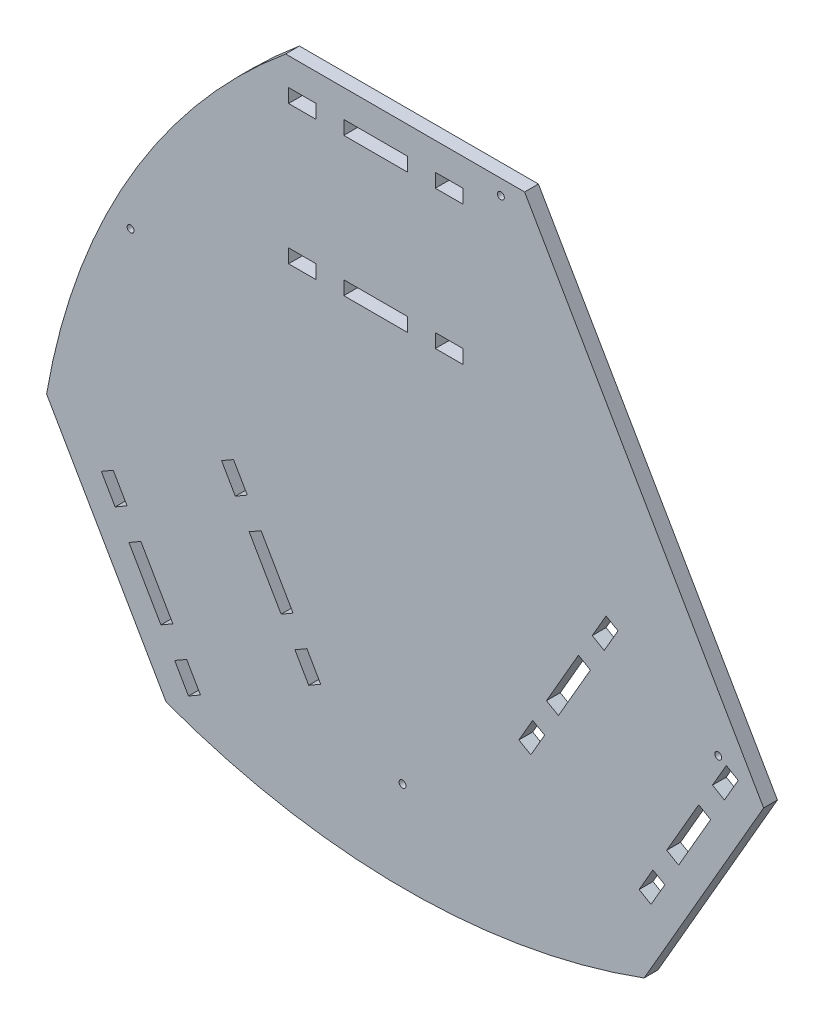
SolidWorks part; units mm, degrees
ref_plane "Front Plane" through (0, 0, 0) normal (0, 0, 1) x (1, 0, 0)
ref_plane "Top Plane" through (0, 0, 0) normal (0, 1, 0) x (1, 0, 0)
ref_plane "Right Plane" through (0, 0, 0) normal (1, 0, 0) x (0, 0, -1)
sketch "Sketch1" plane through (0, 0, 0) normal (0, 0, 1) x (0.866, -0.5, 0)
  line L0 (125, -43.3013) -> (125, 43.3013)
  line L1 (-100, 86.6025) -> (-100, -86.6025)
  line L2 (-25, -129.9038) -> (125, -43.3013)
  line L3 (125, 43.3013) -> (-25, 129.9038)
  line L4 (-25, 129.9038) -> (-100, 86.6025)
  line L5 (-100, -86.6025) -> (-25, -129.9038)
  circle A0 centre (0, 0) radius 100 construction
  dimension "D1" = 200
  dimension "D2" = 225
  dimension "D3" = 3
extrude "Boss-Extrude1" add sketch "Sketch1" along normal blind 5
sketch "Sketch2" plane through (0, 0, 5) normal (0, 0, 1) x (1, 0, 0)
  line L0 (7.45, 112.5) -> (13.95, 112.5) construction
  line L1 (-25, 107.5) -> (25, 107.5)
  line L2 (-25, 107.5) -> (-25, 67.5)
  line L3 (-25, 67.5) -> (25, 67.5)
  line L4 (25, 107.5) -> (25, 67.5)
  line L5 (-42.2219, 115) -> (-37.2219, 115)
  line L6 (-42.2219, 115) -> (-42.2219, 110)
  line L7 (-42.2219, 110) -> (-37.2219, 110)
  line L8 (-37.2219, 115) -> (-37.2219, 110)
  line L9 (-24.55, 115) -> (-14.55, 115)
  line L10 (-105.5977, -32.0994) -> (-45.9567, -55.4006) construction
  line L11 (105.5977, -32.0994) -> (80.5977, -75.4006)
  line L12 (105.5977, -32.0994) -> (70.9567, -12.0994)
  line L13 (70.9567, -12.0994) -> (45.9567, -55.4006)
  line L14 (80.5977, -75.4006) -> (45.9567, -55.4006)
  line L15 (-24.55, 115) -> (-24.55, 110)
  line L16 (-24.55, 110) -> (-14.55, 110)
  line L17 (-14.55, 115) -> (-14.55, 110)
  line L18 (-2.55, 115) -> (7.45, 115)
  line L19 (-2.55, 115) -> (-2.55, 110)
  line L20 (-80.5977, -75.4006) -> (-105.5977, -32.0994)
  line L21 (-80.5977, -75.4006) -> (-45.9567, -55.4006)
  line L22 (-45.9567, -55.4006) -> (-70.9567, -12.0994)
  line L23 (-105.5977, -32.0994) -> (-70.9567, -12.0994)
  line L24 (-2.55, 110) -> (7.45, 110)
  line L25 (7.45, 115) -> (7.45, 110)
  line L26 (-42.2219, 64.6999) -> (-37.2219, 64.6999)
  line L27 (-42.2219, 64.6999) -> (-42.2219, 59.6999)
  line L28 (-42.2219, 59.6999) -> (-37.2219, 59.6999)
  line L29 (129.9038, -25) -> (43.3013, 125) construction
  line L30 (-43.3013, 125) -> (-129.9038, -25) construction
  line L31 (-86.6025, -100) -> (86.6025, -100) construction
  line L32 (25, 107.5) -> (-25, 67.5) construction
  line L33 (0, 87.5) -> (0, 0) construction
  line L34 (7.6967, 67.9809) -> (20.9943, 63.1068) construction
  line L35 (7.8225, 62.7206) -> (21.1202, 63.0915) construction
  line L36 (7.85, 67.9634) -> (21.1477, 67.9634) construction
  line L37 (21.0421, 67.9704) -> (21.0421, 63.0963) construction
  line L38 (7.7445, 67.9755) -> (7.7445, 62.7305) construction
  line L39 (-62.783, -27.1834) -> (-69.4318, -15.6673) construction
  line L40 (-62.7408, -27.2808) -> (-58.1985, -24.6583) construction
  line L41 (-58.2289, -24.5858) -> (-65.1989, -13.2552) construction
  line L42 (-69.3851, -15.7622) -> (-65.1641, -13.3251) construction
  line L43 (-62.7215, -27.325) -> (-65.1493, -13.3718) construction
  line L44 (54.9962, -40.6947) -> (50.454, -38.0722) construction
  line L45 (54.933, -40.78) -> (48.2842, -52.2961) construction
  line L46 (50.4064, -38.1348) -> (44.0788, -49.8363) construction
  line L47 (48.343, -52.2082) -> (44.1219, -49.7712) construction
  line L48 (55.0249, -40.656) -> (44.155, -49.735) construction
  line L49 (-37.2219, 64.6999) -> (-37.2219, 59.6999)
  line L50 (-24.55, 64.6999) -> (-14.55, 64.6999)
  line L51 (-24.55, 64.6999) -> (-24.55, 59.6999)
  line L52 (-24.55, 59.6999) -> (-14.55, 59.6999)
  line L53 (-14.55, 64.6999) -> (-14.55, 59.6999)
  line L54 (-2.55, 64.6999) -> (7.45, 64.6999)
  line L55 (-2.55, 64.6999) -> (-2.55, 59.6999)
  line L56 (-2.55, 59.6999) -> (7.45, 59.6999)
  line L57 (7.45, 64.6999) -> (7.45, 59.6999)
  line L58 (7.45, 62.1999) -> (13.95, 62.1999) construction
  line L59 (77.1428, 4.2153) -> (74.6428, -0.1148)
  line L60 (77.1428, 4.2153) -> (72.8126, 6.7153)
  line L61 (72.8126, 6.7153) -> (70.3126, 2.3852)
  line L62 (74.6428, -0.1148) -> (70.3126, 2.3852)
  line L63 (68.3068, -11.0891) -> (63.3068, -19.7493)
  line L64 (68.3068, -11.0891) -> (63.9767, -8.5891)
  line L65 (63.9767, -8.5891) -> (58.9767, -17.2493)
  line L66 (63.3068, -19.7493) -> (58.9767, -17.2493)
  line L67 (57.3068, -30.1416) -> (52.3068, -38.8019)
  line L68 (57.3068, -30.1416) -> (52.9767, -27.6416)
  line L69 (52.9767, -27.6416) -> (47.9767, -36.3019)
  line L70 (52.3068, -38.8019) -> (47.9767, -36.3019)
  line L71 (50.1417, -37.5519) -> (46.8917, -43.181) construction
  line L72 (120.7039, -20.9347) -> (118.2039, -25.2649)
  line L73 (120.7039, -20.9347) -> (116.3738, -18.4347)
  line L74 (116.3738, -18.4347) -> (113.8738, -22.7649)
  line L75 (118.2039, -25.2649) -> (113.8738, -22.7649)
  line L76 (111.8679, -36.2391) -> (106.8679, -44.8993)
  line L77 (111.8679, -36.2391) -> (107.5378, -33.7391)
  line L78 (107.5378, -33.7391) -> (102.5378, -42.3993)
  line L79 (106.8679, -44.8993) -> (102.5378, -42.3993)
  line L80 (100.8679, -55.2916) -> (95.8679, -63.9519)
  line L81 (100.8679, -55.2916) -> (96.5378, -52.7916)
  line L82 (96.5378, -52.7916) -> (91.5378, -61.4519)
  line L83 (95.8679, -63.9519) -> (91.5378, -61.4519)
  line L84 (93.7029, -62.7019) -> (90.4529, -68.3311) construction
  line L85 (-34.9208, -68.9152) -> (-37.4208, -64.5851)
  line L86 (-34.9208, -68.9152) -> (-30.5907, -66.4152)
  line L87 (-30.5907, -66.4152) -> (-33.0907, -62.0851)
  line L88 (-37.4208, -64.5851) -> (-33.0907, -62.0851)
  line L89 (-43.7568, -53.6109) -> (-48.7568, -44.9506)
  line L90 (-43.7568, -53.6109) -> (-39.4267, -51.1109)
  line L91 (-39.4267, -51.1109) -> (-44.4267, -42.4506)
  line L92 (-48.7568, -44.9506) -> (-44.4267, -42.4506)
  line L93 (-54.7568, -34.5583) -> (-59.7568, -25.8981)
  line L94 (-54.7568, -34.5583) -> (-50.4267, -32.0583)
  line L95 (-50.4267, -32.0583) -> (-55.4267, -23.3981)
  line L96 (-59.7568, -25.8981) -> (-55.4267, -23.3981)
  line L97 (-57.5917, -24.6481) -> (-60.8417, -19.0189) construction
  line L98 (-78.482, -94.0653) -> (-80.982, -89.7351)
  line L99 (-78.482, -94.0653) -> (-74.1518, -91.5653)
  line L100 (-74.1518, -91.5653) -> (-76.6518, -87.2351)
  line L101 (-80.982, -89.7351) -> (-76.6518, -87.2351)
  line L102 (-87.3179, -78.7609) -> (-92.3179, -70.1007)
  line L103 (-87.3179, -78.7609) -> (-82.9878, -76.2609)
  line L104 (-82.9878, -76.2609) -> (-87.9878, -67.6007)
  line L105 (-92.3179, -70.1007) -> (-87.9878, -67.6007)
  line L106 (-98.3179, -59.7084) -> (-103.3179, -51.0481)
  line L107 (-98.3179, -59.7084) -> (-93.9878, -57.2084)
  line L108 (-93.9878, -57.2084) -> (-98.9878, -48.5481)
  line L109 (-103.3179, -51.0481) -> (-98.9878, -48.5481)
  line L110 (-101.1529, -49.7981) -> (-104.4029, -44.1689) construction
  line L111 (70.9567, -12.0994) -> (80.5977, -75.4006) construction
  line L112 (0, 0) -> (-75.7772, -43.75) construction
  line L113 (0, 0) -> (75.7772, -43.75) construction
  line L114 (118.2039, -25.2649) -> (113.8738, -22.7649) construction
  line L115 (118.2039, -25.2649) -> (115.8679, -29.3109) construction
  circle A2 centre (0, 0) radius 100 construction
  circle A3 centre (13.95, 112.5) radius 1.5
  circle A4 centre (13.95, 62.1999) radius 1.5
  circle A5 centre (46.8917, -43.181) radius 1.5
  circle A6 centre (90.4529, -68.3311) radius 1.5
  circle A7 centre (-60.8417, -19.0189) radius 1.5
  circle A8 centre (-104.4029, -44.1689) radius 1.5
  circle A11 centre (90.4529, -68.3311) radius 1.5
  circle A14 centre (-104.4029, -44.1689) radius 1.5
  circle A15 centre (69.3097, -4.3519) radius 1.5 [skipped]
  circle A16 centre (112.8708, -29.502) radius 1.5 [skipped]
  circle A17 centre (-38.4238, -57.848) radius 1.5 [skipped]
  circle A18 centre (-81.9849, -82.998) radius 1.5 [skipped]
  circle A19 centre (-30.886, 112.5) radius 1.5 [skipped]
  circle A20 centre (-30.886, 62.1999) radius 1.5 [skipped]
  point P4 (-63.6967, -19.9081)
  point P5 (49.0893, -45.2089)
  point P47 (14.6074, 65.117)
  dimension "D5" = 3
  dimension "D1" = 87.5
  dimension "D2" = 3
  dimension "D3" = 40
  dimension "D4" = 50
  dimension "D6" = 6.5
  dimension "D7" = 3
  dimension "D8" = 3
extrude "Cut-Extrude1" [suppressed] cut sketch "Sketch2" against normal blind 5 contours L4 L1 L2 L3 | L17 L9 L15 L16 | L25 L18 L19 L24 | A3 | L49 L26 L27 L28 | L53 L50 L51 L52 | L57 L54 L55 L56 | A4 | L14 L11 L12 L13 | L23 L20 L21 L22 | L96 L93 L94 L95 | L92 L89 L90 L91 | L88 L85 L86 L87 | A8 | A7 | L62 L59 L60 L61 | L66 L63 L64 L65 | L70 L67 L68 L69 | L75 L72 L73 L74 | L79 L76 L77 L78 | L83 L80 L81 L82 | L7 L8 L5 L6 | L106 L109 L108 L107 | L103 L104 L105 L102 | L98 L101 L100 L99 | A5 | A6
sketch "Sketch3" plane through (0, 0, 5) normal (0, 0, 1) x (1, 0, 0)
  line L12 (-86.6025, -100) -> (86.6025, -100)
  line L13 (86.6025, -100) -> (129.9038, -25)
  line L14 (129.9038, -25) -> (43.3013, 125)
  line L15 (43.3013, 125) -> (-43.3013, 125)
  line L16 (-43.3013, 125) -> (-129.9038, -25)
  line L17 (-129.9038, -25) -> (-86.6025, -100)
  line L18 (-86.6025, -100) -> (86.6025, -100)
  line L19 (86.6025, -100) -> (129.9038, -25)
  line L20 (129.9038, -25) -> (43.3013, 125)
  line L21 (43.3013, 125) -> (-43.3013, 125)
  line L22 (-43.3013, 125) -> (-129.9038, -25)
  line L23 (-129.9038, -25) -> (-86.6025, -100)
  dimension "D1" = 0
extrude "Boss-Extrude2" add sketch "Sketch3" against normal blind 5
sketch "Sketch4" plane through (0, 0, 5) normal (0, 0, 1) x (1, 0, 0)
  line L0 (-32.2219, 110) -> (-32.2219, 115) construction
  line L1 (-42.2219, 110) -> (-32.2219, 110)
  line L2 (-42.2219, 110) -> (-42.2219, 115)
  line L3 (-42.2219, 115) -> (-32.2219, 115)
  line L4 (20.95, 110) -> (20.95, 115)
  line L5 (10.95, 115) -> (20.95, 115)
  line L6 (-32.2219, 115) -> (-32.2219, 110)
  line L7 (10.95, 110) -> (20.95, 110)
  line L8 (-22.2219, 115) -> (-22.2219, 110)
  line L9 (-42.2219, 59.6999) -> (-32.2219, 59.6999)
  line L10 (0.95, 115) -> (0.95, 110)
  line L12 (10.95, 115) -> (10.95, 110)
  line L13 (-22.2219, 110) -> (-22.2219, 115) construction
  line L14 (0.95, 110) -> (0.95, 115) construction
  line L15 (10.95, 110) -> (10.95, 115) construction
  line L16 (-22.2219, 115) -> (0.95, 115)
  line L17 (-22.2219, 110) -> (0.95, 110)
  line L18 (-42.2219, 59.6999) -> (-42.2219, 64.6999)
  line L19 (-42.2219, 64.6999) -> (-32.2219, 64.6999)
  line L20 (20.95, 59.6999) -> (20.95, 64.6999)
  line L21 (10.95, 64.6999) -> (20.95, 64.6999)
  line L22 (-32.2219, 64.6999) -> (-32.2219, 59.6999)
  line L23 (10.95, 59.6999) -> (20.95, 59.6999)
  line L24 (-22.2219, 64.6999) -> (-22.2219, 59.6999)
  line L25 (0.95, 64.6999) -> (0.95, 59.6999)
  line L26 (10.95, 64.6999) -> (10.95, 59.6999)
  line L27 (-22.2219, 64.6999) -> (0.95, 64.6999)
  line L28 (-22.2219, 59.6999) -> (0.95, 59.6999)
  line L29 (116.3738, -18.4347) -> (111.3738, -27.095)
  line L30 (116.3738, -18.4347) -> (120.7039, -20.9347)
  line L31 (120.7039, -20.9347) -> (115.7039, -29.595)
  line L32 (84.7878, -73.1432) -> (89.1179, -75.6432)
  line L33 (94.1179, -66.983) -> (89.1179, -75.6432)
  line L34 (115.7039, -29.595) -> (111.3738, -27.095)
  line L35 (89.7878, -64.483) -> (84.7878, -73.1432)
  line L36 (110.7039, -38.2552) -> (106.3738, -35.7552)
  line L37 (72.8126, 6.7153) -> (67.8126, -1.945)
  line L38 (99.1179, -58.3227) -> (94.7878, -55.8227)
  line L39 (94.1179, -66.983) -> (89.7878, -64.483)
  line L40 (110.7039, -38.2552) -> (99.1179, -58.3227)
  line L41 (106.3738, -35.7552) -> (94.7878, -55.8227)
  line L42 (72.8126, 6.7153) -> (77.1428, 4.2153)
  line L43 (77.1428, 4.2153) -> (72.1428, -4.445)
  line L44 (41.2267, -47.9932) -> (45.5568, -50.4932)
  line L45 (50.5568, -41.833) -> (45.5568, -50.4932)
  line L46 (72.1428, -4.445) -> (67.8126, -1.945)
  line L47 (46.2267, -39.333) -> (41.2267, -47.9932)
  line L48 (67.1428, -13.1052) -> (62.8126, -10.6052)
  line L49 (55.5568, -33.1727) -> (51.2267, -30.6727)
  line L50 (50.5568, -41.833) -> (46.2267, -39.333)
  line L51 (67.1428, -13.1052) -> (55.5568, -33.1727)
  line L52 (62.8126, -10.6052) -> (51.2267, -30.6727)
  line L53 (-74.1518, -91.5653) -> (-79.1518, -82.905)
  line L54 (-74.1518, -91.5653) -> (-78.482, -94.0653)
  line L55 (-78.482, -94.0653) -> (-83.482, -85.405)
  line L56 (-105.7378, -36.8568) -> (-110.0679, -39.3568)
  line L57 (-105.0679, -48.017) -> (-110.0679, -39.3568)
  line L58 (-83.482, -85.405) -> (-79.1518, -82.905)
  line L59 (-100.7378, -45.517) -> (-105.7378, -36.8568)
  line L60 (-88.482, -76.7448) -> (-84.1518, -74.2448)
  line L61 (-30.5907, -66.4152) -> (-35.5907, -57.755)
  line L62 (-100.0679, -56.6773) -> (-95.7378, -54.1773)
  line L63 (-105.0679, -48.017) -> (-100.7378, -45.517)
  line L64 (-88.482, -76.7448) -> (-100.0679, -56.6773)
  line L65 (-84.1518, -74.2448) -> (-95.7378, -54.1773)
  line L66 (-30.5907, -66.4152) -> (-34.9208, -68.9152)
  line L67 (-34.9208, -68.9152) -> (-39.9208, -60.255)
  line L68 (-62.1767, -11.7067) -> (-66.5068, -14.2067)
  line L69 (-61.5068, -22.867) -> (-66.5068, -14.2067)
  line L70 (-39.9208, -60.255) -> (-35.5907, -57.755)
  line L71 (-57.1767, -20.367) -> (-62.1767, -11.7067)
  line L72 (-44.9208, -51.5947) -> (-40.5907, -49.0947)
  line L73 (-56.5068, -31.5273) -> (-52.1767, -29.0273)
  line L74 (-61.5068, -22.867) -> (-57.1767, -20.367)
  line L75 (-44.9208, -51.5947) -> (-56.5068, -31.5273)
  line L76 (-40.5907, -49.0947) -> (-52.1767, -29.0273)
  line L77 (10.95, 64.6999) -> (0.95, 64.6999) construction
  line L78 (10.95, 59.6999) -> (10.95, 64.6999) construction
  line L79 (46.2267, -39.333) -> (50.5568, -41.833) construction
  line L80 (46.2267, -39.333) -> (51.2267, -30.6727) construction
  circle A0 centre (0.4282, 0.0852) radius 100 construction
  dimension "D1" = 2
  dimension "D2" = 3
extrude "Cut-Extrude2" cut sketch "Sketch4" against normal blind 5
sketch "Sketch5" plane through (0, 0, 5) normal (0, 0, 1) x (1, 0, 0)
  line L0 (-129.9038, -25) -> (-43.3013, 125)
  line L1 (-43.3013, 125) -> (-41.9709, 125.5807)
  line L2 (86.6025, -100) -> (-86.6025, -100)
  line L3 (-86.6025, -100) -> (-86.5891, -98.5285)
  arc A0 (-129.9038, -25) -> (-43.3013, 125) centre (116.4984, -67.2604) cw
  arc A1 (86.6025, -100) -> (-86.6025, -100) centre (0, 134.5208) cw
  dimension "D1" = 250
extrude "Boss-Extrude3" add sketch "Sketch5" against normal blind 5 contours A0 L0 | A1 L2 region at (-91.9792, 53.1042, 5) region at (0, -106.2084, 5)
sketch "Sketch6" [suppressed] plane through (0, 0, 5) normal (0, 0, 1) x (1, 0, 0)
  line L0 (-37.2219, 115) -> (-24.55, 110) construction
  line L1 (-37.2219, 64.6999) -> (-24.55, 59.6999) construction
  line L2 (118.2039, -25.2649) -> (107.5378, -33.7391) construction
  line L3 (74.6428, -0.1148) -> (63.9767, -8.5891) construction
  line L4 (-80.982, -89.7351) -> (-82.9878, -76.2609) construction
  line L5 (-37.4208, -64.5851) -> (-39.4267, -51.1109) construction
  circle A0 centre (-30.886, 112.5) radius 1.5
  circle A1 centre (-30.886, 62.1999) radius 1.5
  circle A2 centre (112.8708, -29.502) radius 1.5
  circle A3 centre (69.3097, -4.3519) radius 1.5
  circle A4 centre (-81.9849, -82.998) radius 1.5
  circle A5 centre (-38.4238, -57.848) radius 1.5
  dimension "D1" = 3
  dimension "D2" = 3
extrude "Cut-Extrude3" [suppressed] cut sketch "Sketch6" against normal blind 5
sketch "Sketch7" plane through (0, 0, 5) normal (0, 0, 1) x (1, 0, 0)
  line L0 (129.9038, -25) -> (43.3013, 125) construction
  line L1 (-99.4749, 42.0456) -> (34.7071, 119.5156) construction
  line L2 (-99.4749, 42.0456) -> (-20.7349, -94.3361) construction
  line L3 (-20.7349, -94.3361) -> (113.4471, -16.8661) construction
  line L4 (34.7071, 119.5156) -> (113.4471, -16.8661) construction
  circle A0 centre (-99.4749, 42.0456) radius 1.25
  circle A1 centre (34.7071, 119.5156) radius 1.25
  circle A2 centre (113.4471, -16.8661) radius 1.25
  circle A3 centre (34.7071, 119.5156) radius 1.98 construction
  circle A4 centre (113.4471, -16.8661) radius 1.98 construction
  circle A5 centre (-99.4749, 42.0456) radius 1.98 construction
  circle A6 centre (-0.9376, -82.9061) radius 1.25
  dimension "D1" = 2.5
extrude "Cut-Extrude4" cut sketch "Sketch7" against normal blind 5
